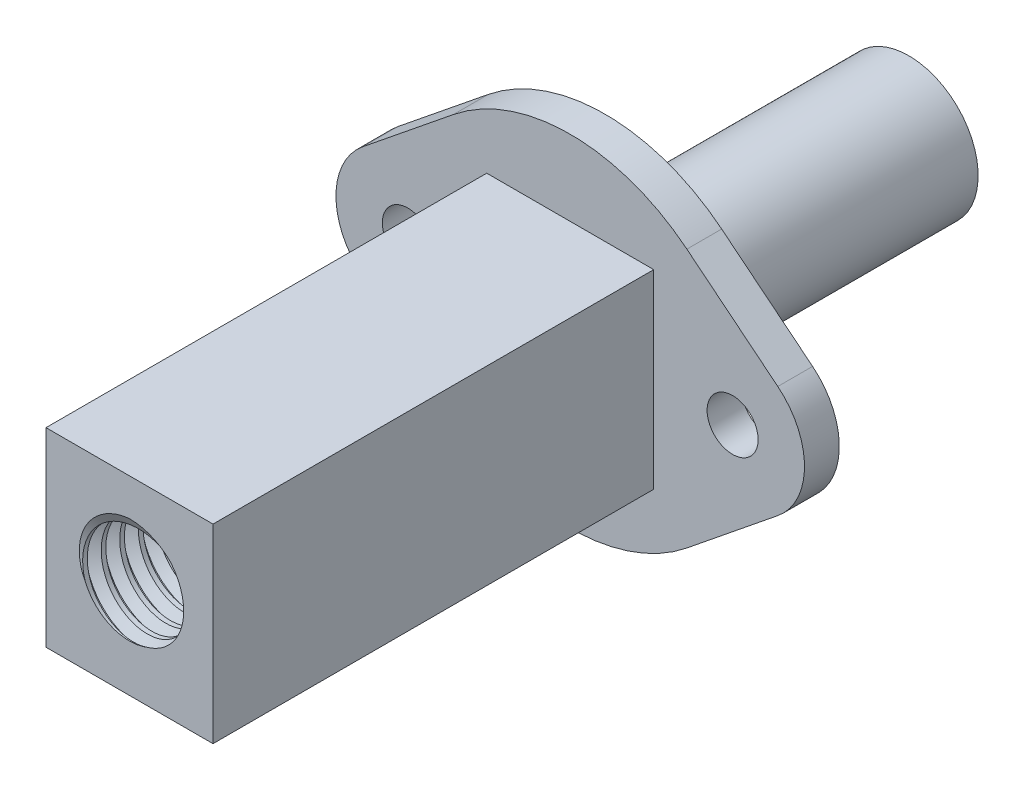
SolidWorks part; units mm, degrees
ref_plane "Front Plane" through (0, 0, 0) normal (0, 0, 1) x (1, 0, 0)
ref_plane "Top Plane" through (0, 0, 0) normal (0, 1, 0) x (1, 0, 0)
ref_plane "Right Plane" through (0, 0, 0) normal (1, 0, 0) x (0, 0, -1)
sketch "Esquisse1" plane through (0, 0, 0) normal (0, 0, 1) x (1, 0, 0)
  line L0 (-3.6, 4.1) -> (3.6, -4.1) construction
  line L1 (-3.6, 4.1) -> (3.6, 4.1)
  line L2 (-3.6, 4.1) -> (-3.6, -4.1)
  line L3 (-3.6, -4.1) -> (3.6, -4.1)
  line L4 (3.6, 4.1) -> (3.6, -4.1)
  dimension "D1" = 8.2
  dimension "D2" = 7.2
extrude "Boss.-Extru.1" add sketch "Esquisse1" along normal blind 19
sketch "Esquisse4" plane through (0, 0, 19) normal (0, 0, 1) x (1, 0, 0)
  circle A0 centre (0, 0) radius 2.5
  dimension "D1" = 5
extrude "Enlèv. mat.-Extru.1" cut sketch "Esquisse4" against normal blind 5
thread "Filetage1" pitch 0.8 method extrude trim with start face yes profile "Thread Profile2" start angle 0, offset 1, length 5, pitch 0.8, diameter 5
ref_plane "Plan2" through (-2.5, 0, 20) normal (0, -1, 0) x (-1, 0, 0)
sketch "Thread Profile2" plane through (-2.5, 0, 20) normal (0, -1, 0) x (-1, 0, 0)
  line L0 (0, 0) -> (0, 0.8) construction
  line L11 (0, 0) -> (0, 0.7)
  line L12 (0, 0.7) -> (-0.433, 0.45)
  line L13 (-0.433, 0.45) -> (-0.433, 0.25)
  line L15 (-0.433, 0.25) -> (0, 0)
  line L17 (-0.433, 0.35) -> (0, 0.35) construction
  point P2 (0, 0)
  dimension "Pitch" = 0.8
  dimension "Profile_Angle" = 60
  dimension "Profile_Land" = 0.2
  dimension "Profile_Height" = 0.433
sketch "Esquisse14" plane through (0, 0, 0) normal (0, 0, -1) x (-1, 0, 0)
  line L0 (-7, 0) -> (7, 0) construction
  line L1 (-8.9486, 2.411) -> (-5.0286, 5.5791)
  line L2 (5.0286, 5.5791) -> (8.9486, 2.411)
  line L3 (8.9486, -2.411) -> (5.0286, -5.5791)
  line L4 (-5.0286, -5.5791) -> (-8.9486, -2.411)
  line L5 (0, -9.6432) -> (9.4286, 2.0231) construction
  line L6 (0, 9.6432) -> (0, -9.6432) construction
  line L7 (-7, 0) -> (-8.9486, 2.411) construction
  circle A0 centre (-7, 0) radius 1.1
  circle A1 centre (7, 0) radius 1.1
  arc A2 (-5.0286, 5.5791) -> (5.0286, 5.5791) centre (0, -0.6429) cw
  arc A3 (5.0286, -5.5791) -> (-5.0286, -5.5791) centre (0, 0.6429) cw
  arc A4 (8.9486, 2.411) -> (8.9486, -2.411) centre (7, 0) cw
  arc A5 (-8.9486, 2.411) -> (-8.9486, -2.411) centre (-7, 0) ccw
  dimension "D4" = 2.2
  dimension "D5" = 8
  dimension "D6" = 3.1
  dimension "D1" = 14
  dimension "D2" = 15
  dimension "D3" = 3.1
extrude "Boss.-Extru.2" add sketch "Esquisse14" along normal blind 1.5
sketch "Esquisse15" plane through (0, 0, -1.5) normal (0, 0, -1) x (-1, 0, 0)
  circle A0 centre (0, 0) radius 5
  dimension "D1" = 10
extrude "Boss.-Extru.3" add sketch "Esquisse15" along normal blind 0.5
sketch "Esquisse16" plane through (0, 0, -2) normal (0, 0, -1) x (-1, 0, 0)
  circle A0 centre (0, 0) radius 1.25
  dimension "D1" = 2.5
extrude "Boss.-Extru.4" add sketch "Esquisse16" along normal blind 2
sketch "Esquisse17" plane through (0, 0, -4) normal (0, 0, -1) x (-1, 0, 0)
  circle A0 centre (0, 0) radius 2.985
  dimension "D1" = 5.97
extrude "Boss.-Extru.5" add sketch "Esquisse17" along normal blind 10.6
sketch "Esquisse18" plane through (0, 0, -14.6) normal (0, 0, -1) x (-1, 0, 0)
  circle A0 centre (0, 0) radius 0.875
  dimension "D1" = 1.75
extrude "Enlèv. mat.-Extru.2" cut sketch "Esquisse18" against normal through all
